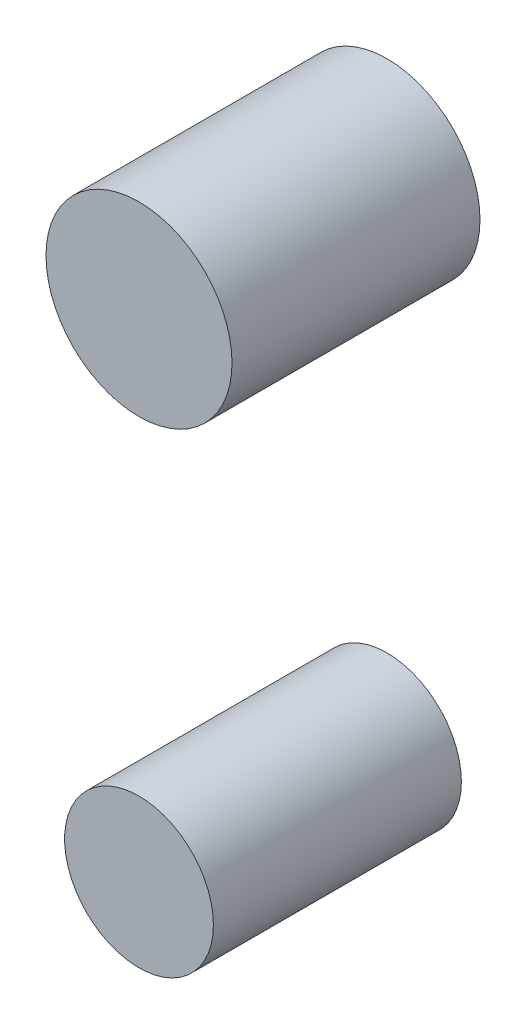
SolidWorks part; units mm, degrees
ref_plane "前视基准面" through (0, 0, 0) normal (0, 0, 1) x (1, 0, 0)
ref_plane "上视基准面" through (0, 0, 0) normal (0, 1, 0) x (1, 0, 0)
ref_plane "右视基准面" through (0, 0, 0) normal (1, 0, 0) x (0, 0, -1)
other "Configuration Table"
sketch "Sketch1" plane through (0, 0, 0) normal (0, 0, 1) x (1, 0, 0)
  circle A0 centre (0, 0) radius 12
  circle A1 centre (0, 80) radius 15
extrude "Boss-Extrude1" add sketch "Sketch1" along normal blind 20 and the other way blind 20
sketch3d "3DSketch1"
  line L0 (0, 0, -100) -> (0, 0, 100) construction
ref_axis "Axis_J4" through (0, 0, -100) along (0, 0, 1)
sketch3d "3DSketch2"
  line L0 (0, 80, -100) -> (0, 80, 100) construction
ref_axis "Axis_J5" through (0, 80, -100) along (0, 0, 1)
ref_plane "Mate_Mid" through (0, 0, 0) normal (0, 0, 1) x (1, 0, 0)
